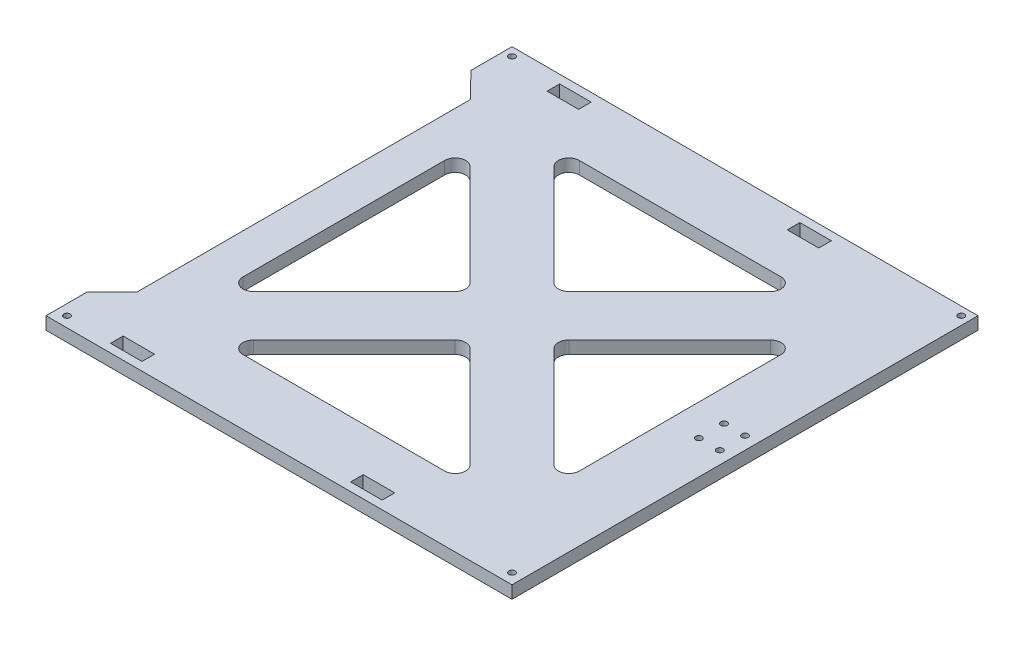
SolidWorks part; units mm, degrees
ref_plane "Спереди" through (0, 0, 0) normal (0, 0, 1) x (1, 0, 0)
ref_plane "Сверху" through (0, 0, 0) normal (0, 1, 0) x (1, 0, 0)
ref_plane "Справа" through (0, 0, 0) normal (1, 0, 0) x (0, 0, -1)
sketch "Эскиз1" plane through (0, 0, 0) normal (0, 1, 0) x (1, 0, 0)
  line L0 (210.5882, 1.4676) -> (-138.0899, 1.4676) construction
  line L1 (-102.7681, -109.5324) -> (-102.7681, -89.9182)
  line L2 (-102.7681, 112.4676) -> (119.2319, 112.4676)
  line L3 (119.2319, 112.4676) -> (119.2319, -109.5324)
  line L4 (-76.0395, 108.4677) -> (-61.0396, 108.4677)
  line L5 (-76.0395, 108.4677) -> (-76.0395, 102.4676)
  line L6 (-76.0395, 102.4676) -> (-61.0396, 102.4676)
  line L7 (-61.0396, 108.4677) -> (-61.0396, 102.4676)
  line L8 (38.3605, 108.4677) -> (53.3604, 108.4677)
  line L9 (38.3605, 108.4677) -> (38.3605, 102.4676)
  line L10 (38.3605, 102.4676) -> (53.3604, 102.4676)
  line L11 (53.3604, 108.4677) -> (53.3604, 102.4676)
  line L12 (53.3604, -105.5325) -> (53.3604, -99.5324)
  line L13 (38.3605, -99.5324) -> (53.3604, -99.5324)
  line L14 (38.3605, -105.5325) -> (38.3605, -99.5324)
  line L15 (38.3605, -105.5325) -> (53.3604, -105.5325)
  line L16 (-61.0396, -105.5325) -> (-61.0396, -99.5324)
  line L17 (-76.0395, -99.5324) -> (-61.0396, -99.5324)
  line L18 (-76.0395, -105.5325) -> (-76.0395, -99.5324)
  line L19 (-76.0395, -105.5325) -> (-61.0396, -105.5325)
  line L20 (-102.7681, -109.5324) -> (119.2319, -109.5324)
  line L21 (-102.7681, 112.4676) -> (119.2319, -109.5324) construction
  line L22 (-102.7681, -109.5324) -> (119.2319, 112.4676) construction
  line L23 (8.2319, 1.4676) -> (8.2319, 124.5614) construction
  line L24 (-15.3036, 5.0031) -> (-63.3366, 53.0361)
  line L25 (-71.8722, 49.5006) -> (-71.8722, -46.5654)
  line L26 (31.7674, 5.0031) -> (79.8004, 53.0361)
  line L27 (88.336, 49.5006) -> (88.336, -46.5654)
  line L28 (4.6964, 25.0031) -> (-43.3366, 73.0361)
  line L29 (-39.8011, 81.5716) -> (56.2649, 81.5716)
  line L30 (59.8004, 73.0361) -> (11.7674, 25.0031)
  line L31 (31.7674, -2.068) -> (79.8004, -50.101)
  line L32 (59.8004, -70.101) -> (11.7674, -22.068)
  line L33 (-39.8011, -78.6365) -> (56.2649, -78.6365)
  line L34 (4.6964, -22.068) -> (-43.3366, -70.101)
  line L35 (-15.3036, -2.068) -> (-63.3366, -50.101)
  line L36 (113.2319, 1.4676) -> (113.2319, 54.2202) construction
  line L37 (103.2319, 1.4676) -> (103.2319, 54.2202) construction
  line L38 (138.7043, 7.4676) -> (96.3994, 7.4676) construction
  line L39 (-102.7681, 92.8533) -> (-90.8805, 80.8494)
  line L40 (-90.8805, 80.8494) -> (-90.8805, -77.9142)
  line L41 (-63.3366, 53.0361) -> (-102.7681, 92.8533) construction
  line L42 (79.8004, 53.0361) -> (119.2319, 92.8533) construction
  line L43 (-102.7681, -89.9182) -> (-90.8805, -77.9142)
  line L44 (-102.7681, 92.8533) -> (-102.7681, 112.4676)
  circle A0 centre (-98.7681, 108.4676) radius 1.5
  circle A1 centre (115.2319, 108.4676) radius 1.5
  circle A2 centre (-97.7681, -104.5324) radius 1.5
  circle A4 centre (114.2319, -104.5324) radius 1.5
  arc A5 (79.8004, 53.0361) -> (88.336, 49.5006) centre (83.336, 49.5006) cw
  arc A6 (4.6964, 25.0031) -> (11.7674, 25.0031) centre (8.2319, 28.5386) ccw
  arc A7 (56.2649, 81.5716) -> (59.8004, 73.0361) centre (56.2649, 76.5716) cw
  arc A8 (-43.3366, 73.0361) -> (-39.8011, 81.5716) centre (-39.8011, 76.5716) cw
  arc A9 (-63.3366, 53.0361) -> (-71.8722, 49.5006) centre (-66.8722, 49.5006) ccw
  arc A10 (79.8004, -50.101) -> (88.336, -46.5654) centre (83.336, -46.5654) ccw
  arc A11 (4.6964, -22.068) -> (11.7674, -22.068) centre (8.2319, -25.6035) cw
  arc A12 (56.2649, -78.6365) -> (59.8004, -70.101) centre (56.2649, -73.6365) ccw
  arc A13 (-43.3366, -70.101) -> (-39.8011, -78.6365) centre (-39.8011, -73.6365) ccw
  arc A14 (-63.3366, -50.101) -> (-71.8722, -46.5654) centre (-66.8722, -46.5654) cw
  arc A15 (31.7674, 5.0031) -> (31.7674, -2.068) centre (35.303, 1.4676) ccw
  arc A16 (-15.3036, 5.0031) -> (-15.3036, -2.068) centre (-18.8392, 1.4676) cw
  circle A17 centre (103.2319, 7.4676) radius 1.5
  circle A18 centre (113.2319, 7.4676) radius 1.5
  circle A19 centre (113.2319, -4.5324) radius 1.5
  circle A20 centre (103.2319, -4.5324) radius 1.5
  point P25 (119.2319, 1.4676)
  point P26 (-102.7681, 1.4676)
  point P45 (88.336, 61.5716)
  point P48 (8.2319, 21.4676)
  point P53 (-51.8722, 81.5716)
  point P56 (-71.8722, 61.5716)
  point P58 (88.336, 1.4676)
  point P72 (-71.8722, 1.4676)
  point P74 (28.2319, 1.4676)
  point P77 (-11.7681, 1.4676)
  point P95 (-90.8805, 1.4676)
  dimension "D3" = 3
  dimension "D4" = 3
  dimension "D5" = 107
  dimension "D7" = 3
  dimension "D8" = 3
  dimension "D13" = 5
  dimension "D14" = 5
  dimension "D18" = 3
  dimension "D19" = 3
  dimension "D1" = 222
  dimension "D2" = 111
  dimension "D6" = 107
  dimension "D9" = 20
  dimension "D10" = 20
  dimension "D11" = 85
  dimension "D12" = 85
  dimension "D15" = 6
  dimension "D16" = 10
  dimension "D17" = 6
  dimension "D20" = 101
  dimension "D21" = 101
extrude "Бобышка-Вытянуть1" add sketch "Эскиз1" along normal blind 6
